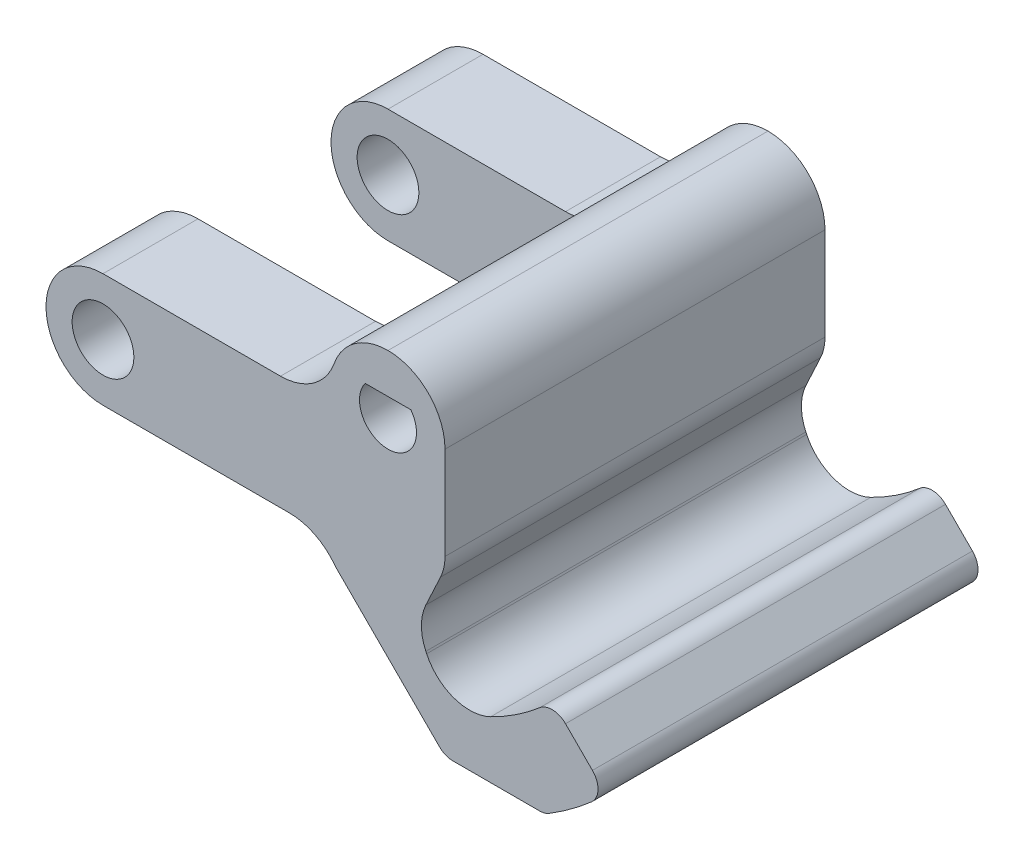
SolidWorks part; units mm, degrees
material "PBT General Purpose"
ref_plane "Front Plane" through (0, 0, 0) normal (0, 0, 1) x (1, 0, 0)
ref_plane "Top Plane" through (0, 0, 0) normal (0, 1, 0) x (1, 0, 0)
ref_plane "Right Plane" through (0, 0, 0) normal (1, 0, 0) x (0, 0, -1)
sketch "Sketch2" plane through (0, 0, 0) normal (0, 0, 1) x (1, 0, 0)
  line L1 (-6, 6) -> (6, 6)
  line L2 (-6, 6) -> (-6, -16)
  line L4 (6, 6) -> (6, -10.8869)
  line L5 (17.3241, -17.3241) -> (22.981, -22.981)
  line L6 (0, 0) -> (17.3241, -17.3241) construction
  line L7 (0, -24.5) -> (0, 0) construction
  line L10 (-6, -16) -> (6, -28)
  line L11 (6, -10.8869) -> (3, -17.3204)
  line L12 (3, -17.3204) -> (6, -23.7539)
  line L13 (6, -28) -> (16.5, -28)
  arc A0 (6, -23.7539) -> (17.3241, -17.3241) centre (0, 0) ccw
  arc A1 (16.5, -28) -> (22.981, -22.981) centre (0, 0) ccw
  circle A2 centre (0, 0) radius 3
  arc A3 (0, -24.5) -> (6, -23.7539) centre (0, 0) ccw construction
  dimension "D2" = 6
  dimension "D5" = 24.5
  dimension "D3" = 12
  dimension "D4" = 45
  dimension "D6" = 8
  dimension "D8" = 45
  dimension "D9" = 25
  dimension "D10" = 25
  dimension "D11" = 3
  dimension "D7" = 28
extrude "Boss-Extrude1" add sketch "Sketch2" along normal mid plane 40
fillet "Fillet1" radius 6 2 edges at (6, 6, 0) (-6, 6, 0)
fillet "Fillet2" radius 2 5 edges at (22.981, -22.981, 0) (17.3241, -17.3241, 0) (-6, -16, 0) (16.5, -28, 0) (6, -28, 0)
fillet "Fillet4" radius 5 3 edges at (6, -10.8869, 0) (3, -17.3204, 0) (6, -23.7539, 0)
sketch "Sketch3" plane through (0, 0, 20) normal (0, 0, 1) x (1, 0, 0)
  line L0 (-6, -2) -> (-36, -2)
  line L1 (-6, 0) -> (-6, -15.1716) construction
  line L2 (-36, -2) -> (-36, -14)
  line L3 (-36, -14) -> (-6, -14)
  line L4 (-6, -14) -> (-6, -2)
  line L5 (-30, -8) -> (-36, -8) construction
  circle A0 centre (-30, -8) radius 3.25
  dimension "D2" = 6
  dimension "D1" = 6.5
  dimension "D3" = 8
  dimension "D4" = 12
  dimension "D5" = 30
extrude "Boss-Extrude2" add sketch "Sketch3" against normal blind 10
fillet "Fillet3" radius 6 4 edges at (-36, -14, 15) (-36, -2, 15) (-6, -14, 15) (-6, -2, 15)
mirror "Mirror1" about plane through (0, 0, 0) normal (0, 0, 1) of "Fillet3", "Boss-Extrude2"
sketch "Sketch4" plane through (0, 0, -20) normal (0, 0, -1) x (-1, 0, 0)
  line L0 (-2.4, 1.8) -> (2.4, 1.8)
  circle A0 centre (0, 0) radius 3 construction
  arc A1 (2.4, 1.8) -> (-2.4, 1.8) centre (0, 0) ccw
  dimension "D1" = 1.8
extrude "Boss-Extrude3" add sketch "Sketch4" against normal up to surface (40 mm away) up to face at (1.1571, -14.8675, 20)
equation "\"D4@Sketch2\"=70-25"
equation "\"D2@Sketch3\"=\"D4@Sketch3\"/2"
